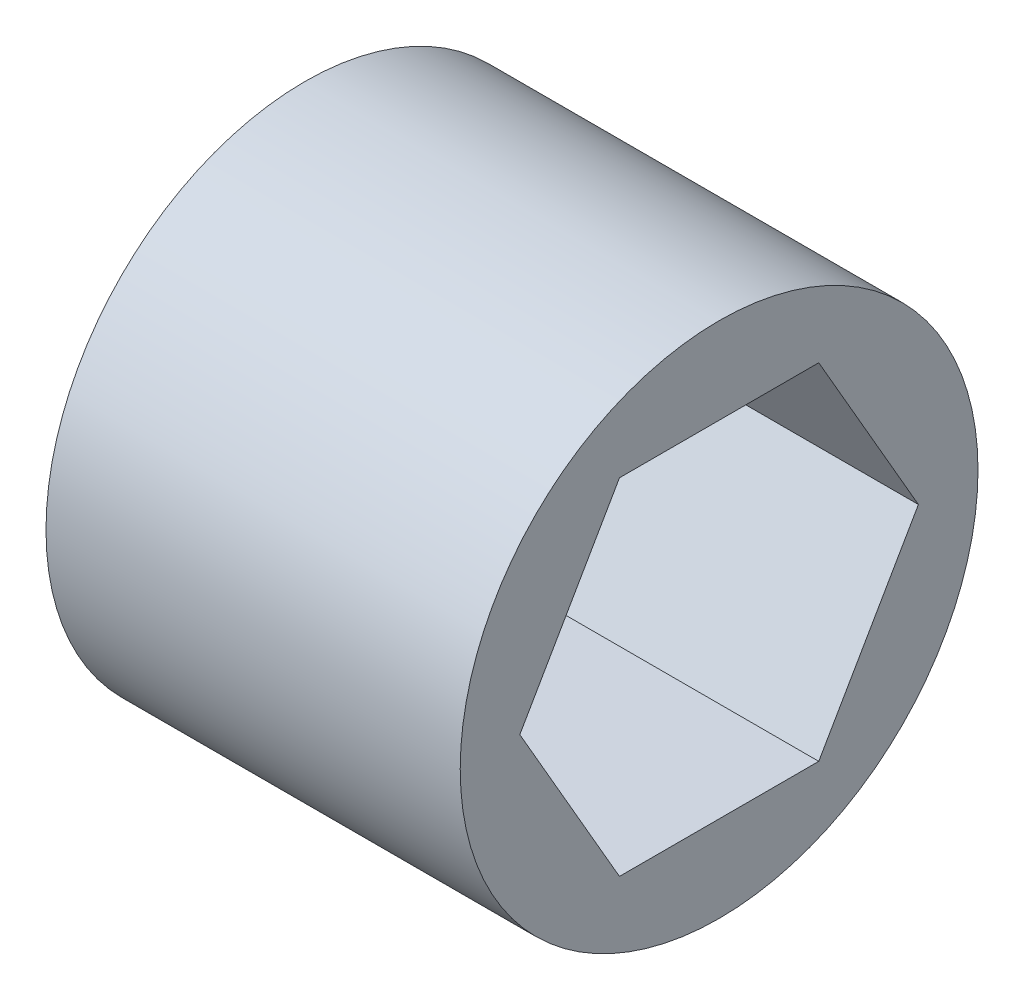
SolidWorks part; units mm, degrees
material "PET"
ref_plane "Front" through (0, 0, 0) normal (0, 0, 1) x (1, 0, 0)
ref_plane "Top" through (0, 0, 0) normal (0, 1, 0) x (1, 0, 0)
ref_plane "Right" through (0, 0, 0) normal (1, 0, 0) x (0, 0, -1)
sketch "Sketch1" plane through (0, 0, 0) normal (1, 0, 0) x (0, 0, -1)
  line L1 (7.3323, 0) -> (3.6662, 6.35)
  line L2 (3.6662, 6.35) -> (-3.6662, 6.35)
  line L3 (-3.6662, 6.35) -> (-7.3323, 0)
  line L4 (-7.3323, 0) -> (-3.6662, -6.35)
  line L5 (-3.6662, -6.35) -> (3.6662, -6.35)
  line L6 (3.6662, -6.35) -> (7.3323, 0)
  circle A0 centre (0, 0) radius 6.35 construction
  circle A1 centre (0, 0) radius 9.525
  dimension "D2" = 19.05
  dimension "D1" = 12.7
extrude "Boss-Extrude1" add sketch "Sketch1" along normal mid plane 15.24
